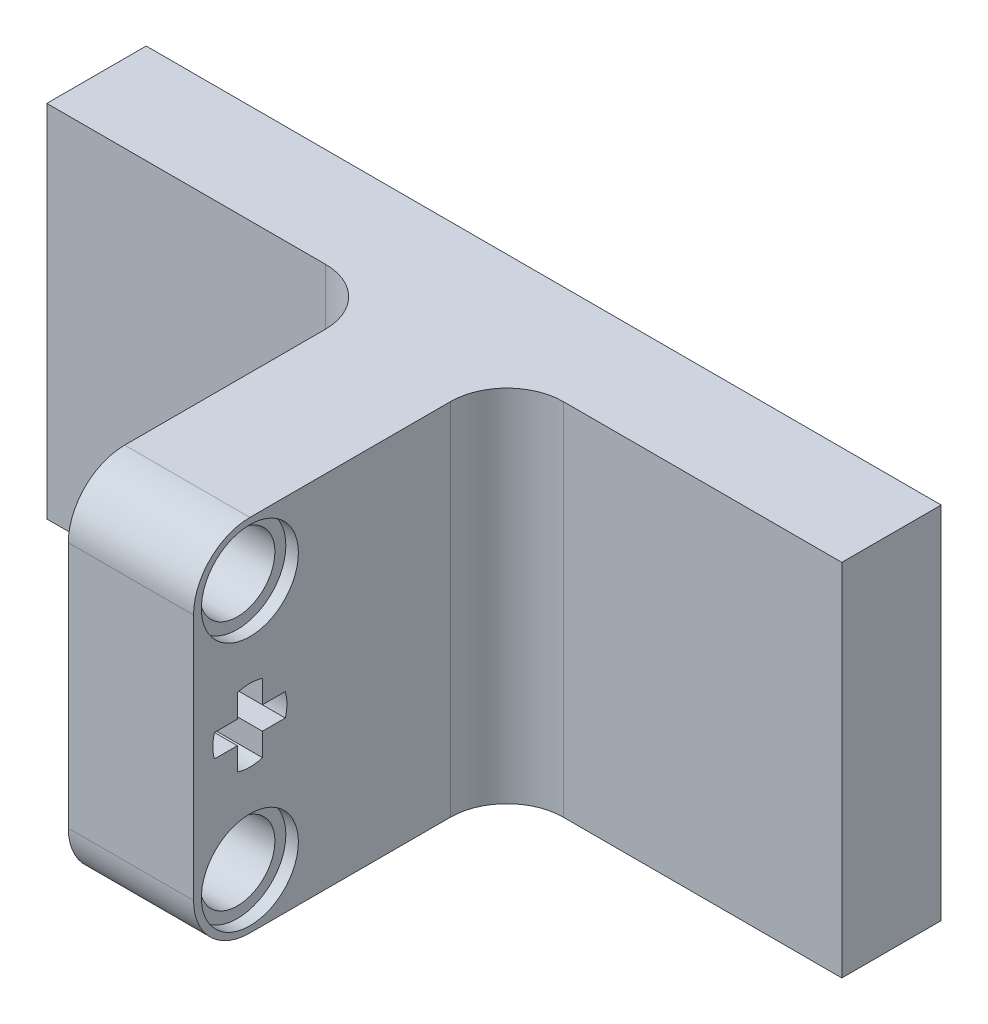
SolidWorks part; units mm, degrees
ref_plane "Front Plane" through (0, 0, 0) normal (0, 0, 1) x (1, 0, 0)
ref_plane "Top Plane" through (0, 0, 0) normal (0, 1, 0) x (1, 0, 0)
ref_plane "Right Plane" through (0, 0, 0) normal (1, 0, 0) x (0, 0, -1)
sketch "Sketch2" plane through (0, 0, 0) normal (0, 1, 0) x (1, 0, 0)
  line L0 (-4, -3.175) -> (-4, -19.6)
  line L1 (-25.4, 3.175) -> (25.4, 3.175)
  line L2 (-25.4, 3.175) -> (-25.4, -3.175)
  line L3 (-25.4, -3.175) -> (-4, -3.175)
  line L4 (25.4, 3.175) -> (25.4, -3.175)
  line L5 (-25.4, 3.175) -> (25.4, -3.175) construction
  line L6 (-25.4, -3.175) -> (25.4, 3.175) construction
  line L8 (4, -19.6) -> (4, -3.175)
  line L9 (4, -3.175) -> (25.4, -3.175)
  line L10 (-4, -19.6) -> (-4, -23.2)
  line L11 (-4, -23.2) -> (4, -23.2)
  line L12 (4, -23.2) -> (4, -19.6)
  point P0 (0, 0)
  point P9 (-4, -23.2)
  point P13 (-4, -19.6)
  dimension "D1" = 50.8
  dimension "D2" = 22.775
  dimension "D3" = 8
  dimension "D4" = 3.6
  dimension "D5" = 6.35
extrude "Boss-Extrude1" add sketch "Sketch2" along normal mid plane 23
sketch "Sketch3" plane through (4, 0, 0) normal (1, 0, 0) x (0, 0, -1)
  line L0 (-20.4, 0.7314) -> (-20.4, 2.1941)
  line L1 (-18.8, 2.1941) -> (-18.8, 0.7314)
  line L2 (-20.4, 0.7314) -> (-18.8, 0.7314) construction
  line L3 (-20.4, 0.7314) -> (-20.4, -0.7314) construction
  line L4 (-20.4, 0.7314) -> (-21.8627, 0.7314)
  line L5 (-21.8627, -0.7314) -> (-20.4, -0.7314)
  line L6 (-20.4, -0.7314) -> (-20.4, -2.1941)
  line L7 (-18.8, -2.1941) -> (-18.8, -0.7314)
  line L8 (-18.8, -0.7314) -> (-17.3373, -0.7314)
  line L9 (-18.8, 0.7314) -> (-17.3373, 0.7314)
  line L10 (-17.3373, 0.7314) -> (-15.4007, 0.7314)
  line L11 (-23.2, 11.5) -> (-23.2, -11.5) construction
  circle A0 centre (-19.6, 0) radius 2.5157 construction
  circle A1 centre (-19.6, 8) radius 3.1
  circle A2 centre (-19.6, -8) radius 3.1
  circle A3 centre (-19.6, 8) radius 2.4
  circle A4 centre (-19.6, -8) radius 2.4
  arc A5 (-20.4, 2.1941) -> (-18.8, 2.1941) centre (-19.6, -0.2798) cw
  arc A6 (-21.8627, 0.7314) -> (-21.8627, -0.7314) centre (-19.3677, 0) ccw
  arc A7 (-20.4, -2.1941) -> (-18.8, -2.1941) centre (-19.6, 0.2798) ccw
  arc A8 (-17.3373, 0.7314) -> (-17.3373, -0.7314) centre (-19.8323, 0) cw
  point P12 (-19.6, 0.7314)
  point P26 (-21.9677, 0)
  point P27 (-19.6, -2.3202)
  point P28 (-17.7465, -0.3678)
  point P29 (0, 0)
  point P30 (0, 0)
  dimension "D1" = 6.2
  dimension "D2" = 4.8
  dimension "D7" = 2.6
  dimension "D3" = 8
  dimension "D4" = 8
  dimension "D5" = 1.4627
  dimension "D6" = 1.6
  dimension "D8" = 3.6
extrude "Cut-Extrude1" cut sketch "Sketch3" against normal through all contours A3 | A8 L9 L1 A5 L0 L4 A6 L5 L6 A7 L7 L8 | A4 region at (4, 0, 19.6) region at (4, 8, 19.6) region at (4, -8, 19.6)
extrude "Cut-Extrude2" cut sketch "Sketch3<3>" against normal blind 0.8 contours A1 A3 | A2 A4 region at (4, 8, 22.6123) region at (4, -8, 22.6123)
sketch "Sketch3<3>" plane through (4, 0, 0) normal (1, 0, 0) x (0, 0, -1) same geometry as "Sketch3"
mirror "Mirror1" about plane through (0, 0, 0) normal (1, 0, 0) of "Cut-Extrude2"
fillet "Fillet1" radius 3.6 4 edges at (0, -11.5, 23.2) (0, 11.5, 23.2) (-4, 0, 3.175) (4, 0, 3.175)
